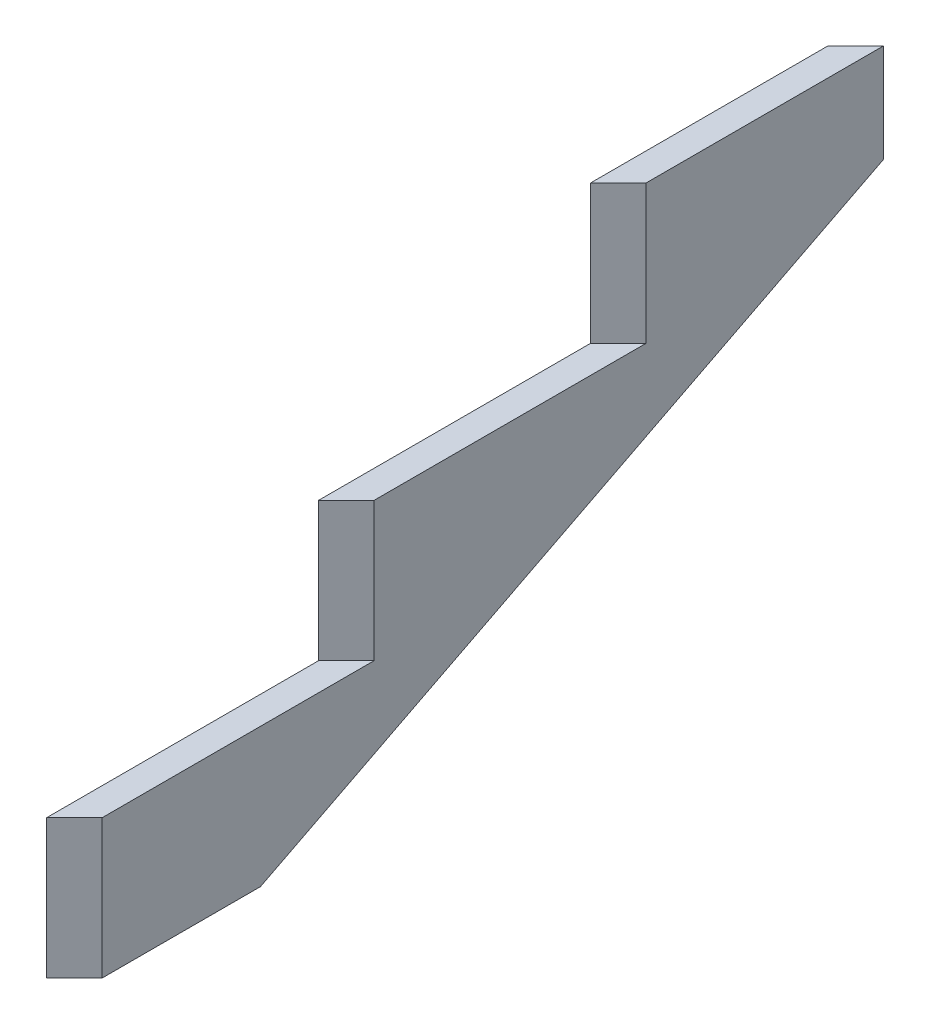
SolidWorks part; units mm, degrees
ref_plane "Front Plane" through (0, 0, 0) normal (0, 0, 1) x (1, 0, 0)
ref_plane "Top Plane" through (0, 0, 0) normal (0, 1, 0) x (1, 0, 0)
ref_plane "Right Plane" through (0, 0, 0) normal (1, 0, 0) x (0, 0, -1)
sketch "Sketch1" plane through (0, 0, 0) normal (1, 0, 0) x (0, 0, -1)
  line L0 (255.1993, 0) -> (1109.6004, 436.5266)
  line L1 (1109.6004, 571.5) -> (745.7205, 571.5)
  line L6 (0, 0) -> (0, 190.5)
  line L7 (0, 190.5) -> (372.8602, 190.5)
  line L10 (372.8602, 190.5) -> (372.8602, 381)
  line L11 (372.8602, 381) -> (745.7205, 381)
  line L14 (745.7205, 381) -> (745.7205, 571.5)
  line L15 (745.7205, 571.5) -> (1109.6004, 571.5)
  line L17 (745.7205, 381) -> (614.1602, 381)
  line L18 (745.7205, 381) -> (745.7205, 571.5)
  line L21 (614.1602, 381) -> (372.8602, 381)
  line L25 (372.8602, 190.5) -> (241.3, 190.5)
  line L26 (372.8602, 190.5) -> (372.8602, 381)
  line L29 (241.3, 190.5) -> (0, 190.5)
  line L34 (0, 0) -> (0, 190.5)
  line L37 (745.7205, 571.5) -> (1109.6004, 571.5)
  line L38 (745.7205, 571.5) -> (745.7205, 381)
  line L40 (1109.6004, 571.5) -> (1109.6004, 436.5266)
  line L41 (0, 0) -> (255.1993, 0)
  line L42 (0, 0) -> (0, 190.5)
  line L43 (0, 190.5) -> (372.8602, 190.5)
  dimension "D1" = 363.88
  dimension "D2" = 190.5
  dimension "D3" = 190.5
  dimension "D4" = 372.8602
  dimension "D5" = 372.8602
  dimension "D6" = 285.75
  dimension "D7" = 134.9734
  dimension "D8" = 571.5
  dimension "D9" = 1109.6004
  dimension "D10" = 285.75
  dimension "D11" = 116.1087
  dimension "D12" = 116.1087
  dimension "D13" = 255.1993
  dimension "D17" = 190.5
extrude "Boss-Extrude2" add sketch "Sketch1" along normal blind 38.1 contours L6 L41 L0 L40 L1 L14 L11 L10 L7 region at (0, 281.8722, -561.8809)
sketch "Sketch2" plane through (0, 571.5, 0) normal (0, 1, 0) x (1, 0, 0)
  line L0 (38.1, 1109.6004) -> (0, 1071.5004)
  line L2 (0, 1109.6004) -> (0, 745.7205) construction
  line L3 (0, 1071.5004) -> (0, 1109.6004)
  line L6 (0, 1109.6004) -> (38.1, 1109.6004)
  line L7 (0, 745.7205) -> (38.1, 783.8205)
  line L8 (38.1, 1109.6004) -> (38.1, 745.7205) construction
  line L9 (38.1, 783.8205) -> (38.1, 745.7205)
  line L10 (38.1, 745.7205) -> (0, 745.7205)
  line M1 (0, 1109.6004) -> (0, 745.7205)
  line M2 (0, 745.7205) -> (38.1, 745.7205)
  line M3 (38.1, 745.7205) -> (38.1, 1109.6004)
  line M4 (38.1, 1109.6004) -> (0, 1109.6004)
sketch "Sketch3" plane through (0, 381, 0) normal (0, 1, 0) x (1, 0, 0)
  line L0 (0, 372.8602) -> (38.1, 410.9602)
  line L2 (38.1, 372.8602) -> (38.1, 745.7205) construction
  line L3 (38.1, 410.9602) -> (38.1, 372.8602)
  line L4 (38.1, 372.8602) -> (0, 372.8602)
extrude "Cut-Extrude4" cut sketch "Sketch3" against normal up to surface (190.5 mm away) up to face at (19.05, 190.5, -186.4301)
sketch "Sketch4" plane through (0, 190.5, 0) normal (0, 1, 0) x (1, 0, 0)
  line L0 (0, 0) -> (38.1, 38.1)
  line L2 (38.1, 0) -> (38.1, 410.9602) construction
  line L3 (38.1, 38.1) -> (38.1, 0)
  line L4 (38.1, 0) -> (0, 0)
extrude "Cut-Extrude5" cut sketch "Sketch4" against normal up to surface (190.5 mm away) up to face at (19.05, 0, -127.5996)
extrude "Cut-Extrude6" cut sketch "Sketch2" against normal up to next contours L0 M4 M1 region at (12.7, 571.5, -1096.9004)
extrude "Cut-Extrude7" cut sketch "Sketch2<5>" against normal up to surface (190.5 mm away) contours L7 M2 M3 region at (25.4, 571.5, -758.4205) up to face at (19.05, 381, -568.8154)
sketch "Sketch2<5>" plane through (0, 571.5, 0) normal (0, 1, 0) x (1, 0, 0) same geometry as "Sketch2"
